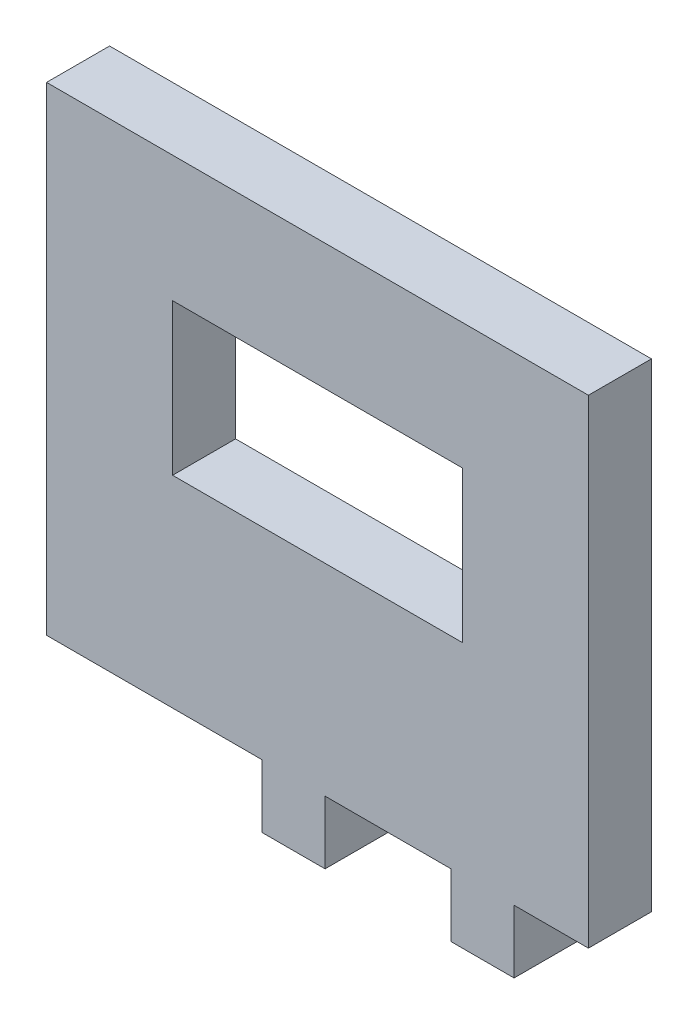
SolidWorks part; units mm, degrees
ref_plane "Front Plane" through (0, 0, 0) normal (0, 0, 1) x (1, 0, 0)
ref_plane "Top Plane" through (0, 0, 0) normal (0, 1, 0) x (1, 0, 0)
ref_plane "Right Plane" through (0, 0, 0) normal (1, 0, 0) x (0, 0, -1)
sketch "Sketch1" plane through (0, 0, 0) normal (0, 0, 1) x (1, 0, 0)
  line L0 (0, 0) -> (-15.8779, 0) construction
  line L1 (-17.1, -6) -> (5.9, -6)
  line L2 (-17.1, -6) -> (-17.1, 6)
  line L3 (-17.1, 6) -> (5.9, 6)
  line L4 (5.9, -6) -> (5.9, 6)
  line L5 (-17.1, -6) -> (5.9, 6) construction
  line L6 (-17.1, 6) -> (5.9, -6) construction
  line L7 (0, 0) -> (0, 16.675) construction
  line L8 (0, -22) -> (0, -10.7792) construction
  line L9 (-27.1, -22) -> (-10, -22)
  line L10 (-27.1, -22) -> (-27.1, 16)
  line L11 (-27.1, 16) -> (15.9, 16)
  line L12 (15.9, -22) -> (15.9, 16)
  line L13 (-27.1, -22) -> (15.9, 16) construction
  line L14 (-27.1, 16) -> (15.9, -22) construction
  line L15 (-1.5, -22) -> (-5, -22)
  line L16 (-5, -27) -> (-10, -27)
  line L17 (-10, -27) -> (-10, -22)
  line L18 (-5, -27) -> (-5, -22)
  line L19 (1.5, -22) -> (5, -22)
  line L20 (5, -22) -> (5, -27)
  line L21 (5, -27) -> (10, -27)
  line L22 (10, -27) -> (10, -22)
  line L23 (-5, -22) -> (5, -22)
  line L24 (10, -22) -> (15.9, -22)
  line L25 (-1.5, -22) -> (1.5, -22)
  circle A0 centre (0, 0) radius 5 construction
  point P0 (-5.6, 0)
  point P9 (-5.6, -3)
  point P15 (0, 0)
  point P16 (0, 0)
  dimension "D1" = 10
  dimension "D2" = 5.9
  dimension "D3" = 17.1
  dimension "D4" = 12
  dimension "D5" = 10
  dimension "D6" = 10
  dimension "D7" = 10
  dimension "D8" = 22
  dimension "D9" = 10
  dimension "D10" = 5
  dimension "D11" = 5
extrude "Boss-Extrude2" add sketch "Sketch1" along normal blind 5 contours L22 L24 L12 L11 L10 L9 L17 L16 L18 L15 L23 L19 L20 L21 L4 L1 L2 L3 region at (-26.4919, -3, 0)
